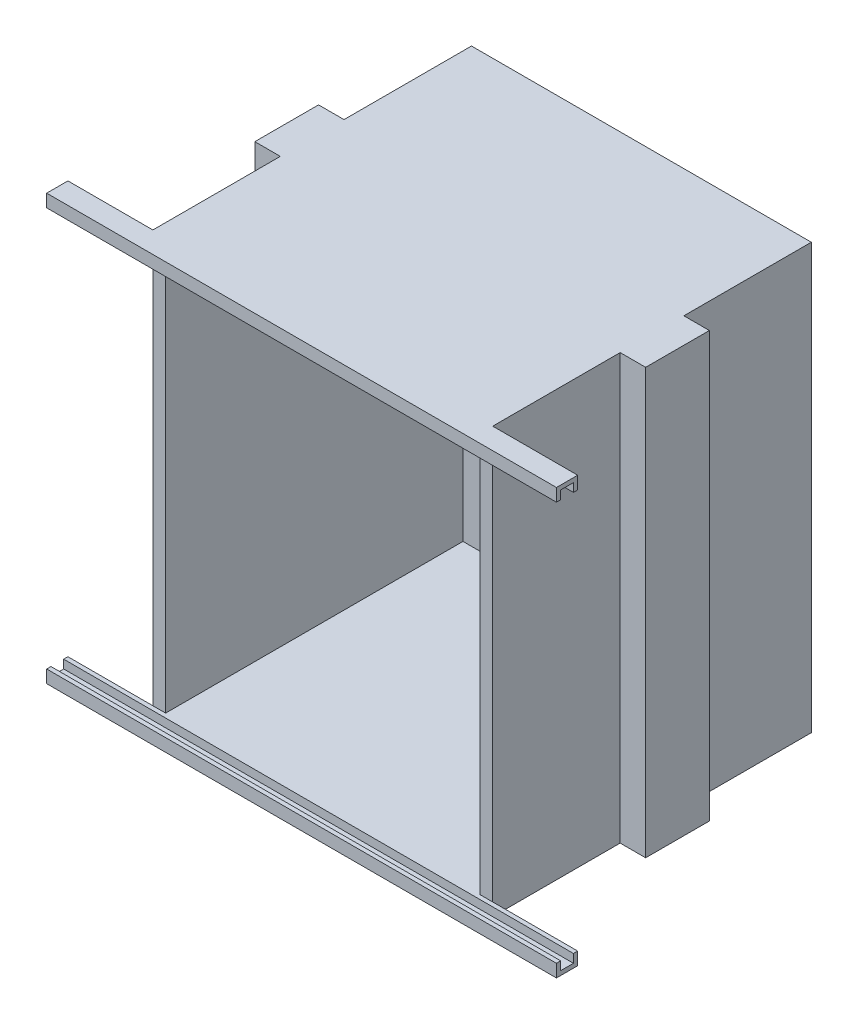
SolidWorks part; units mm, degrees
ref_plane "Plan de face" through (0, 0, 0) normal (0, 0, 1) x (1, 0, 0)
ref_plane "Plan de dessus" through (0, 0, 0) normal (0, 1, 0) x (1, 0, 0)
ref_plane "Plan de droite" through (0, 0, 0) normal (1, 0, 0) x (0, 0, -1)
sketch "Esquisse1" plane through (0, 0, 0) normal (0, 0, 1) x (1, 0, 0)
  line L1 (0, 0) -> (80, 0)
  line L2 (0, 0) -> (0, 100)
  line L3 (0, 100) -> (80, 100)
  line L4 (80, 0) -> (80, 100)
  dimension "D1" = 100
  dimension "D2" = 80
extrude "Boss.-Extru.1" add sketch "Esquisse1" along normal blind 5
sketch "Esquisse2" plane through (0, 0, 5) normal (0, 0, 1) x (1, 0, 0)
  line L1 (0, 100) -> (80, 100)
  line L2 (0, 100) -> (0, 0)
  line L3 (0, 0) -> (80, 0)
  line L4 (80, 100) -> (80, 0)
  line L5 (3, 97) -> (77, 97)
  line L6 (3, 97) -> (3, 3)
  line L7 (3, 3) -> (77, 3)
  line L8 (77, 97) -> (77, 3)
  dimension "D1" = 3
  dimension "D2" = 3
  dimension "D3" = 3
  dimension "D4" = 3
extrude "Boss.-Extru.2" add sketch "Esquisse2" along normal blind 70
sketch "Esquisse3" plane through (0, 0, 75) normal (0, 0, 1) x (1, 0, 0)
  line L0 (80, 0) -> (80, 100) construction
  line L1 (0, 100) -> (80, 100)
  line L2 (0, 100) -> (0, 97)
  line L3 (0, 97) -> (80, 97)
  line L4 (80, 100) -> (80, 97)
  line L5 (3, 3) -> (77, 3) construction
  line L6 (0, 0) -> (80, 0)
  line L7 (0, 0) -> (0, 3)
  line L8 (0, 3) -> (80, 3)
  line L9 (80, 0) -> (80, 3)
  line L10 (77, 97) -> (3, 97) construction
extrude "Boss.-Extru.3" add sketch "Esquisse3" along normal blind 5
sketch "Esquisse4" plane through (80, 0, 0) normal (1, 0, 0) x (0, 0, -1)
  line L0 (-80, 0) -> (0, 0) construction
  line L1 (-80, 100) -> (-75, 100)
  line L2 (-80, 100) -> (-80, 97)
  line L3 (-80, 97) -> (-75, 97)
  line L4 (-75, 100) -> (-75, 97)
  line L5 (-80, 3) -> (-75, 3)
  line L6 (-80, 3) -> (-80, 0)
  line L7 (-80, 0) -> (-75, 0)
  line L8 (-75, 3) -> (-75, 0)
extrude "Boss.-Extru.4" add sketch "Esquisse4" along normal blind 20
sketch "Esquisse5" plane through (0, 0, 0) normal (-1, 0, 0) x (0, 0, 1)
  line L0 (80, 0) -> (0, 0) construction
  line L1 (80, 100) -> (75, 100)
  line L2 (80, 100) -> (80, 97)
  line L3 (80, 97) -> (75, 97)
  line L4 (75, 100) -> (75, 97)
  line L5 (80, 3) -> (75, 3)
  line L6 (80, 3) -> (80, 0)
  line L7 (80, 0) -> (75, 0)
  line L8 (75, 3) -> (75, 0)
extrude "Boss.-Extru.5" add sketch "Esquisse5" along normal blind 20
sketch "Esquisse6" plane through (-20, 0, 0) normal (-1, 0, 0) x (0, 0, 1)
  line L0 (80, 3) -> (75, 3) construction
  line L1 (76, 3) -> (79, 3)
  line L2 (76, 3) -> (76, 1)
  line L3 (76, 1) -> (79, 1)
  line L4 (79, 3) -> (79, 1)
  line L5 (75, 3) -> (75, 0) construction
  line L6 (75, 0) -> (80, 0) construction
  line L7 (75, 97) -> (80, 97) construction
  line L8 (76, 97) -> (79, 97)
  line L9 (76, 97) -> (76, 99)
  line L10 (76, 99) -> (79, 99)
  line L11 (79, 97) -> (79, 99)
  line L12 (75, 100) -> (75, 97) construction
  line L13 (80, 100) -> (75, 100) construction
  point P18 (77.5, 100)
  dimension "D1" = 1
  dimension "D2" = 3
  dimension "D3" = 1
  dimension "D4" = 1
  dimension "D5" = 1
  dimension "D6" = 3
extrude "Enlèv. mat.-Extru.1" cut sketch "Esquisse6" against normal through all
sketch "Esquisse7" plane through (0, 100, 0) normal (0, 1, 0) x (1, 0, 0)
  line L0 (0, -75) -> (0, 0) construction
  line L1 (0, -30) -> (-6, -30)
  line L2 (0, -30) -> (0, -45)
  line L3 (0, -45) -> (-6, -45)
  line L4 (-6, -30) -> (-6, -45)
  line L6 (80, 0) -> (0, 0) construction
  line L8 (80, -75) -> (80, 0) construction
  line L9 (80, -30) -> (86, -30)
  line L10 (80, -30) -> (80, -45)
  line L11 (80, -45) -> (86, -45)
  line L12 (86, -30) -> (86, -45)
  dimension "D1" = 30
  dimension "D2" = 15
  dimension "D3" = 6
  dimension "D4" = 30
  dimension "D5" = 6
  dimension "D6" = 15
extrude "Boss.-Extru.6" add sketch "Esquisse7" against normal up to surface (100 mm away) up to face at (40, 0, 57.5)
